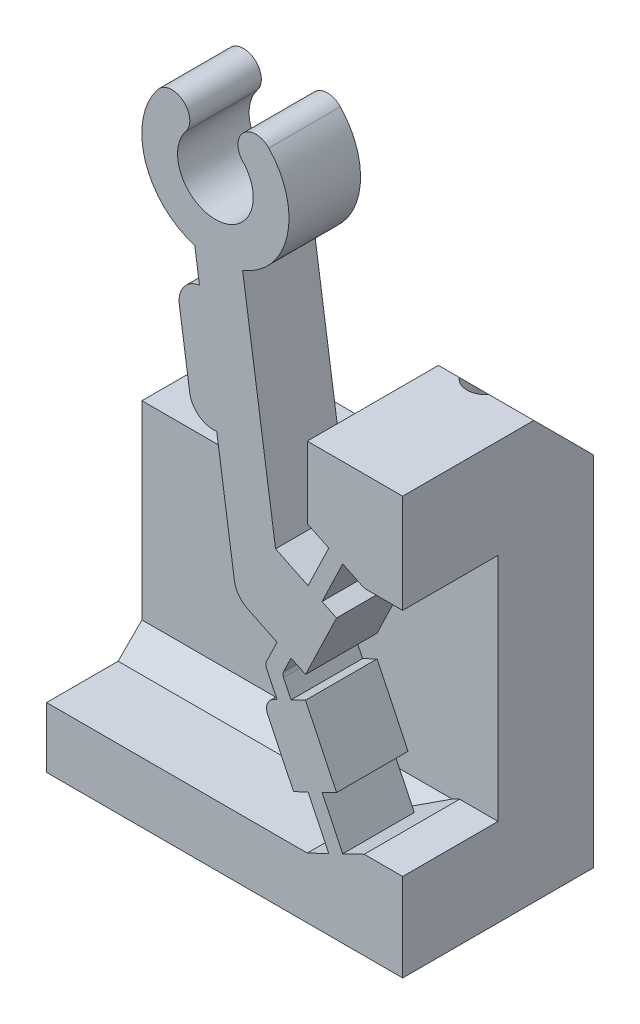
SolidWorks part; units mm, degrees
material "Nylon 6/12"
ref_plane "Front Plane" through (0, 0, 0) normal (0, 0, 1) x (1, 0, 0)
ref_plane "Top Plane" through (0, 0, 0) normal (0, 1, 0) x (1, 0, 0)
ref_plane "Right Plane" through (0, 0, 0) normal (1, 0, 0) x (0, 0, -1)
sketch "Sketch-SkeletonConfigUp" plane through (0, 0, 0) normal (0, 0, 1) x (1, 0, 0)
  line L0 (0, 0) -> (0, -50000) construction
  line L1 (2.4126, 7.5458) -> (2.4126, 0) construction
  line L2 (9.851, 11.9559) -> (4.5811, 12.0511) construction
  line L3 (4.5811, 12.0511) -> (2.4126, 7.5458) construction
  line L4 (2.4126, 7.5458) -> (4.5811, 3.0406) construction
  line L5 (4.5811, 12.0511) -> (6.3534, 17.2104) construction
  line L6 (2.4126, 7.5458) -> (-0.0324, 24.2377) construction
  line L7 (4.5811, 3.0406) -> (9.851, 11.9559) construction
  line L8 (-491.6261, -836.43) -> (9.851, 11.9559) construction
  line L9 (4.5811, 12.0511) -> (4.5811, 3.0406) construction
  line L10 (4.5811, 3.0406) -> (4.5811, -2.3626) construction
  line L11 (0, 0) -> (4.5811, 0) construction
  point P12 (0, 0)
  point P15 (2.4126, 7.9774)
  point P16 (4.5811, 2.192)
  point P17 (0, 0)
  dimension "D4" = 5.2707
  dimension "D5" = 119.553
  dimension "D7" = 5.4552
  dimension "D10" = 6.745
  dimension "D11" = 145.964
  dimension "D2" = 4.5811
  dimension "D3" = 2.1685
  dimension "D6" = 5
  dimension "D9" = 8.333
  dimension "D8" = 16.87
  dimension "D13" = 9.0105
  dimension "D12" = 3.0406
sketch "Sketch-SkeletonConfigDown" plane through (0, 0, 0) normal (0, 0, 1) x (1, 0, 0)
  line L0 (0, 0) -> (0, -50000) construction
  line L1 (4.5811, 12.0511) -> (4.5811, 3.0406) construction
  line L2 (9.851, 11.9559) -> (4.5811, 12.0511) construction
  line L3 (4.5811, 12.0511) -> (6.7497, 7.5458) construction
  line L4 (6.7497, 7.5458) -> (4.5811, 3.0406) construction
  line L5 (4.5811, 12.0511) -> (1.6542, 16.6546) construction
  line L6 (6.7497, 7.5458) -> (-7.8216, 16.0472) construction
  line L7 (4.5811, 3.0406) -> (9.851, 11.9559) construction
  line L8 (-477.4576, -812.4602) -> (9.851, 11.9559) construction
  line L10 (2.4126, 7.5458) -> (4.5811, 3.0406) construction
  line L11 (4.5811, 12.0511) -> (2.4126, 7.5458) construction
  line L12 (2.4126, 7.5458) -> (-0.0324, 24.2377) construction
  line L13 (4.5811, 12.0511) -> (6.3534, 17.2104) construction
  point P2 (4.7163, 6.3999)
  point P3 (4.5811, 1.9514)
  point P11 (5.1631, 6.5275)
  point P12 (4.5811, 9.9521)
  point P15 (4.5811, 13.1402)
  point P16 (6.2686, 7.5458)
  dimension "D4" = 5.2707
  dimension "D5" = 119.553
  dimension "D10" = 6.745
  dimension "D11" = 145.964
  dimension "D12" = 59.739
  dimension "D2" = 59.739
ref_plane "Plane-Cam Base" through (12.592, 0, 0) normal (1, 0, 0) x (0, 0, -1)
ref_plane "Plane-Down-to-Up Derailleur Clearance" through (10.092, 0, 0) normal (1, 0, 0) x (0, 0, -1)
ref_plane "Plane-Cam Cavity Roof" through (8.592, 0, 0) normal (1, 0, 0) x (0, 0, -1)
sketch "Sketch-SwitchBossUp" plane through (0, 0, 0) normal (0, 0, 1) x (1, 0, 0)
  line L8 (-0.8973, 21.2738) -> (-0.7004, 19.9295)
  line L9 (2.4126, 7.5458) -> (-0.0324, 24.2377) construction
  line L15 (2.5535, 6.5038) -> (3.1392, 6.7857) construction
  line L16 (2.4126, 7.5458) -> (4.5811, 3.0406) construction
  line L19 (3.8546, 11.291) -> (4.4403, 11.0091) construction
  line L22 (4.722, 13.0931) -> (5.3077, 12.8112) construction
  line L23 (2.5535, 8.5878) -> (1.9453, 8.8806)
  line L32 (4.874, 3.1815) -> (4.2883, 2.8996) construction
  line L40 (2.0519, 7.5458) -> (2.7733, 7.5458) construction
  line L66 (-0.0324, 27.8193) -> (-0.0324, 50027.8193) construction
  line L74 (-1.1101, 15.8268) -> (-1.5449, 18.7952)
  line L81 (6.2087, 2.7142) -> (10.695, 2.7142)
  line L82 (2.0299, 15.0897) -> (2.4901, 11.9478) construction
  line L88 (3.8209, 16.5268) -> (7.1146, 16.5268)
  line L92 (4.3979, 5.7269) -> (2.5958, 4.8595) construction
  line L95 (2.0299, 15.0897) -> (1.1101, 21.3694) construction
  line L96 (10.695, 2.7142) -> (10.695, 3.0949) construction
  line L97 (1.57, 18.2295) -> (0.9411, 17.592) construction
  line L101 (2.8463, 6.6448) -> (2.4126, 7.5458) construction
  line L103 (-0.0324, 24.2377) -> (1.6643, 25.8455) construction
  line L107 (2.5535, 8.5878) -> (3.1392, 8.3059) construction
  line L109 (-0.0324, 24.2377) -> (-1.8559, 25.7002) construction
  line L114 (3.7474, 7.0785) -> (3.1392, 6.7857)
  line L115 (7.1146, 16.5268) -> (13.4267, 16.5268)
  line L116 (13.4267, 16.5268) -> (13.4267, -0.9732)
  line L117 (13.4267, -0.9732) -> (5.2774, -0.9732)
  line L119 (10.695, 12.3775) -> (10.695, 2.7142)
  line L122 (4.722, 1.9985) -> (3.8209, 1.5648)
  line L123 (5.3077, 2.2805) -> (6.2087, 2.7142)
  line L125 (12.072, 7.7768) -> (13.4267, 7.7768) construction
  line L127 (3.1392, 8.3059) -> (3.7474, 8.0132)
  line L133 (4.2883, 12.1921) -> (4.874, 11.9101) construction
  line L134 (3.7474, 8.0132) -> (5.0485, 10.7163)
  line L135 (4.4403, 11.0091) -> (5.0485, 10.7163)
  line L142 (3.8209, 1.5648) -> (3.8209, -0.9732)
  line L143 (12.0045, 19.1883) -> (12.0045, 16.6962) construction
  line L145 (12.0045, 16.6883) -> (12.0045, -49992.0368) construction
  line L150 (3.8209, -0.9732) -> (5.2774, -0.9732)
  line L152 (4.722, 13.0931) -> (3.8546, 11.291)
  line L153 (5.3077, 12.8112) -> (4.4403, 11.0091)
  line L169 (3.8546, 3.8007) -> (4.722, 1.9985)
  line L170 (5.3077, 2.2805) -> (4.4403, 4.0826)
  line L177 (4.4403, 4.0826) -> (3.8546, 3.8007) construction
  line L191 (2.5535, 6.5038) -> (1.9453, 6.2111)
  line L207 (12.0045, 16.6962) -> (12.0045, 16.6883) construction
  line L209 (12.0045, 19.1883) -> (12.0045, 16.6883) construction
  line L217 (3.8546, 11.291) -> (2.4901, 11.9478)
  line L218 (4.4403, 4.0826) -> (5.0485, 4.3753)
  line L225 (2.4901, 11.9478) -> (1.1101, 21.3694)
  line L226 (3.8209, 13.5268) -> (3.8209, 16.5268)
  line L235 (-0.7004, 19.9295) -> (0.8401, 9.4125) construction
  line L236 (1.9453, 6.2111) -> (3.2464, 3.5079)
  line L237 (0.8401, 9.4125) -> (0.0243, 14.9823)
  line L241 (2.4126, 7.5458) -> (2.8463, 8.4469) construction
  line L243 (3.1392, 6.7857) -> (2.8255, 7.4374)
  line L244 (2.8255, 7.6543) -> (3.1392, 8.3059)
  line L245 (2.5535, 6.5038) -> (2.1041, 7.4374)
  line L246 (2.1041, 7.6543) -> (2.5535, 8.5878)
  line L247 (3.7474, 7.0785) -> (5.0485, 4.3753)
  line L248 (4.722, 1.9985) -> (5.3077, 2.2805) construction
  line L249 (3.8546, 3.8007) -> (3.2464, 3.5079)
  line L250 (1.9453, 8.8806) -> (3.2464, 11.5838) construction
  line L251 (4.5811, 12.0511) -> (2.4126, 7.5458) construction
  line L252 (2.5958, 10.2322) -> (4.3979, 9.3648) construction
  line L253 (3.2464, 11.5838) -> (2.4901, 11.9478) construction
  line L254 (1.9453, 8.8806) -> (0.8401, 9.4125)
  line L255 (4.722, 13.0931) -> (3.8209, 13.5268)
  line L256 (5.3077, 12.8112) -> (6.2087, 12.3775)
  line L257 (6.2087, 12.3775) -> (10.695, 12.3775)
  arc A0 (1.1101, 21.3694) -> (2.2088, 26.3614) centre (-0.0324, 24.2377) ccw
  arc A1 (-0.8973, 21.2738) -> (-2.4409, 26.1694) centre (-0.0324, 24.2377) cw
  arc A2 (-2.4409, 26.1694) -> (-1.2708, 25.2309) centre (-1.8559, 25.7002) cw
  arc A3 (2.2088, 26.3614) -> (1.1199, 25.3296) centre (1.6643, 25.8455) ccw
  arc A4 (-1.2708, 25.2309) -> (1.1199, 25.3296) centre (-0.0324, 24.2377) ccw
  arc A19 (-1.5449, 18.7952) -> (-0.7004, 19.9295) centre (-0.5554, 18.9401) cw
  circle A28 centre (-0.0324, 24.2377) radius 2.3375 construction
  arc A30 (-1.1101, 15.8268) -> (0.0243, 14.9823) centre (-0.1207, 15.9718) ccw
  arc A31 (2.8255, 7.4374) -> (2.8255, 7.6543) centre (3.0507, 7.5458) cw
  arc A32 (2.1041, 7.4374) -> (2.1041, 7.6543) centre (2.3294, 7.5458) cw
  point P3 (3.8091, 13.5268)
  point P5 (0, 0)
  point P6 (3.4969, 5.2932)
  point P7 (0, 0)
  point P16 (3.7601, 13.5561)
  point P28 (3.5462, 1.7741)
  point P33 (6.1777, 2.8466)
  point P37 (5.8406, 2.6366)
  point P45 (3.4969, 9.7985)
  point P50 (3.9347, 1.6196)
  point P52 (3.8382, 1.5732)
  point P54 (5.9324, 2.5678)
  point P66 (4.5811, 6.2164)
  point P165 (4.5811, 12.0511)
  dimension "D23" = 1.5875
  dimension "D24" = 0.75
  dimension "D21" = 0.25
  dimension "D9" = 17.5
  dimension "D8" = 0.65
  dimension "D27" = 0.65
  dimension "D26" = 2
  dimension "D3" = 1
  dimension "D5" = 1
  dimension "D16" = 2
  dimension "D28" = 2
  dimension "D18" = 3
  dimension "D29" = 2
  dimension "D30" = 1
  dimension "D31" = 5
  dimension "D4" = 0.8393
  dimension "D6" = 0.65
  dimension "D7" = 2
  dimension "D11" = 1
extrude "Boss-Switch Body" add sketch "Sketch-SwitchBossUp" along normal blind 3
sketch "Sketch1" plane through (0, 0, 0) normal (0, 0, -1) x (-1, 0, 0)
  line L0 (-7.8209, 2.7142) -> (-3.8209, 2.7142)
  line L1 (-7.8209, -0.9732) -> (-3.8209, -0.9732)
  line L2 (-7.8209, -0.9732) -> (-7.8209, 2.7142)
  line L4 (-3.8209, -0.9732) -> (-3.8209, 2.7142)
  line L5 (-3.8209, 12.3775) -> (-7.8209, 12.3775)
  line L10 (-7.8209, 12.3775) -> (-7.8209, 16.5268)
  line L12 (-7.8209, 16.5268) -> (-3.8209, 16.5268)
  line L14 (-3.8209, 16.5268) -> (-3.8209, 12.3775)
  line L20 (-6.2087, 2.7142) -> (-10.695, 2.7142) construction
  line L22 (-3.8209, -0.9732) -> (-13.4267, -0.9732) construction
  line L26 (-10.695, 12.3775) -> (-6.2087, 12.3775) construction
  line L32 (-3.8209, 1.5648) -> (-3.8209, -0.9732) construction
  point P1 (-7.8209, 2.6731)
  point P7 (-6.2087, 2.7142)
  point P8 (-3.8209, 1.5648)
  point P14 (-3.8209, 2.7142)
  point P18 (-3.7911, 1.5648)
  point P19 (-3.647, 2.4782)
  point P23 (-3.8209, 2.6758)
  dimension "D4" = 4
extrude "Boss-Flange Width" add sketch "Sketch1" along normal blind 5
ref_plane "Plane-Sta2Sit Groove" through (-0.0324, 0, 0) normal (1, 0, 0) x (0, 0, -1)
ref_plane "Plane-Cam Outer Surface" through (-12.1124, 0, 0) normal (1, 0, 0) x (0, 0, -1)
ref_plane "Plane-FlangeTop" through (-7.1124, 0, 0) normal (1, 0, 0) x (0, 0, -1)
sketch "Sketch2" plane through (-7.1124, 0, 0) normal (1, 0, 0) x (0, 0, -1)
  line L0 (5, 16.5268) -> (-3, 16.5268) construction
  line L1 (5, 12.3775) -> (1, 12.3775)
  line L2 (5, 12.3775) -> (5, 16.5268)
  line L3 (5, 16.5268) -> (1, 16.5268)
  line L4 (1, 12.3775) -> (1, 16.5268)
  line L5 (5, 12.3775) -> (0, 12.3775) construction
  line L10 (-3, -0.9732) -> (-3, 16.5268) construction
  line L11 (5, 1.5648) -> (-3, 1.5648)
  line L12 (5, 1.5648) -> (5, -0.9732)
  line L13 (5, -0.9732) -> (-3, -0.9732)
  line L14 (-3, 1.5648) -> (-3, -0.9732)
  line L15 (0, 7.5458) -> (0, 24.2377) construction
  line L17 (5, 2.7142) -> (5, -0.9732) construction
  line L19 (-3, 1.5648) -> (0, 1.5648) construction
  dimension "D1" = 1
extrude "Boss-Flange Height" add sketch "Sketch2" along normal up to surface (11.7404 mm away)
sketch "Sketch17" plane through (0, 1.5648, 0) normal (0, -1, 0) x (1, 0, 0)
  line L0 (7.8209, -5) -> (-7.1124, -5)
  line L1 (7.8209, -5) -> (-7.1124, -5) construction
  line L2 (-7.1124, -5) -> (-7.1124, -1)
  line L3 (-7.1124, -1) -> (7.8209, -1)
  line L4 (7.8209, -1) -> (7.8209, -5)
  line L5 (-7.1124, -1) -> (-7.1124, -5) construction
  line L6 (7.8209, -5) -> (7.8209, 0) construction
  line L7 (3.8209, -1) -> (-7.1124, -1) construction
extrude "Boss-Flange Support" add sketch "Sketch17" against normal up to surface (10.8127 mm away) up to face at (4.3619, 12.3775, -0.5)
sketch "Sketch27" plane through (0, 0, 0) normal (0, 0, 1) x (1, 0, 0)
  line L1 (3.8209, 13.5268) -> (6.2087, 12.3775)
  line L2 (6.2087, 12.3775) -> (3.8209, 12.3775)
  line L5 (3.8209, 12.3775) -> (3.8209, 13.5268)
  line L6 (3.8209, 12.3775) -> (7.8209, 12.3775) construction
  line L7 (6.2087, 12.3775) -> (5.0989, 12.3775) construction
  line L8 (6.2087, 2.7142) -> (3.8209, 2.7142)
  line L9 (3.8209, 2.7142) -> (3.8209, 1.5648)
  line L10 (3.8209, 1.5648) -> (6.2087, 2.7142)
extrude "Cut-Wall Gap" cut sketch "Sketch27" against normal up to surface (1 mm away) up to face at (2.0876, 8.2958, -1)
sketch "Sketch26" plane through (0, 0, -1) normal (0, 0, 1) x (1, 0, 0)
  line L0 (3.8209, 16.5268) -> (-7.1124, 16.5268)
  line L1 (-7.1124, 16.5268) -> (-7.1124, 10.5268)
  line L2 (-7.1124, 16.5268) -> (-7.1124, 1.5648) construction
  line L3 (-7.1124, 10.5268) -> (3.8209, 10.5268)
  line L4 (3.8209, 10.5268) -> (3.8209, 16.5268)
  dimension "D1" = 6
extrude "Cut-Cam Slope Clearance" cut sketch "Sketch26" against normal through all
ref_plane "Plane-Tap Depth" through (0, 5.5268, 0) normal (0, 1, 0) x (1, 0, 0)
sketch "Sketch-HolePositions" plane through (0, -0.9732, 0) normal (0, -1, 0) x (1, 0, 0)
  line L0 (-7.1124, -3) -> (7.8209, -3) construction
  line L1 (7.8209, -5) -> (-7.1124, -5) construction
  line L2 (7.8209, -5) -> (7.8209, 0) construction
  line L4 (-7.1124, -22.2167) -> (-7.1124, 22.2167) construction
  point P6 (-4.1124, -3)
  point P7 (5.3209, -3)
  dimension "D1" = 3
  dimension "D2" = 2.5
  dimension "D3" = 2
sketch "Sketch6" plane through (0, -0.9732, 0) normal (0, -1, 0) x (-1, 0, 0)
  point P0 (4.1124, 3)
  point P3 (-5.3209, 3)
hole_wizard "Tap Drill for M2x0.4 Tap1" positions "Sketch6" profile "Sketch5" hole size "M2x0.4" standard "ANSI Metric" end condition through all
sketch "Sketch5" plane through (-4.1124, -0.9732, -3) normal (1, 0, 0) x (0, 0, -1)
  line L0 (0, 0) -> (0, 27.5687)
  line L1 (0, 27.5687) -> (0.8, 27.5687)
  line L2 (0.8, 27.5687) -> (0.8, 0)
  line L5 (0.8, 0) -> (0, 0)
  line L11 (0, -6.35) -> (0, 107.95) construction
  dimension "Thru Hole Dia." = 1.6
  dimension "Thru Hole Depth" = 27.5687
sketch "Sketch9" plane through (0, -0.9732, 0) normal (0, -1, 0) x (1, 0, 0)
  point P0 (-4.1124, -3)
  point P3 (5.3209, -3)
hole_wizard "M2 Clearance Hole2" positions "Sketch9" profile "Sketch8" hole size "M2" standard "ANSI Metric"
sketch "Sketch8" plane through (-4.1124, -0.9732, -3) normal (1, 0, 0) x (0, 0, -1)
  line L0 (0, 0) -> (0, 7.221)
  line L1 (0, 7.221) -> (1.2, 6.5)
  line L2 (1.2, 6.5) -> (1.2, 0)
  line L5 (1.2, 0) -> (0, 0)
  line L10 (0, 7.221) -> (-1.2, 6.5) construction
  line L11 (0, -6.35) -> (0, 107.95) construction
  dimension "Hole Dia." = 2.4
  dimension "Hole Depth" = 6.5
  dimension "Drill Angle" = 118
sketch "Sketch-Measurements for Derailleur Ramps" [suppressed] plane through (0, 0, 0) normal (0, 0, 1) x (1, 0, 0)
  line L0 (2.8784, 16.9852) -> (4.2265, 19.8331)
  line L1 (3.5524, 18.4092) -> (3.0492, 18.6474)
  line L2 (1.9779, 11.0613) -> (4.4465, 28.5428) construction
  line L3 (3.0492, 18.6474) -> (-4.0642, 13.8428)
  line L4 (7.1843, 11.0614) -> (-9.9544, 15.2993) construction
  line L5 (3.0492, 18.6474) -> (2.1536, 12.3053)
  line L6 (2.1536, 12.3053) -> (-4.0642, 13.8428)
  line L7 (-0.5075, 16.2451) -> (-0.5075, 18.6474)
  line L8 (-0.5075, 18.6474) -> (3.0492, 18.6474)
  line L9 (7.1843, 11.0614) -> (1.9779, 11.0613)
  line L10 (5.8827, 8.6389) -> (3.2795, 8.6389)
  line L12 (7.1843, 11.0614) -> (4.5811, 6.2164) construction
  line L13 (4.5811, 8.6389) -> (4.5811, 8.7912)
  line L14 (4.5811, 6.2164) -> (5.8827, 8.6389)
  line L15 (1.9779, 11.0613) -> (4.5811, 6.2164) construction
  line L16 (3.2795, 8.6389) -> (4.5811, 6.2164)
  line L17 (5.8827, 8.6389) -> (5.8827, 8.7912)
  dimension "D1" = 3.5567
  dimension "D2" = 1.3016
sketch "Sketch12" [suppressed] plane through (0, 23.1883, 0) normal (0, 1, 0) x (1, 0, 0)
  line L0 (10.0045, 0) -> (12.0045, -3)
  line L1 (12.0045, -3) -> (12.0045, 0)
  line L2 (12.0045, 0) -> (10.0045, 0)
extrude "Cut-Up-to-Down Cantilever Slope" [suppressed] cut sketch "Sketch12" against normal up to next
ref_plane "Plane1" [suppressed] through (0, 6.9404, 0) normal (0, 1, 0) x (1, 0, 0)
sketch "Sketch-Derailleur Location" [suppressed] plane through (0, 6.9404, 0) normal (0, 1, 0) x (1, 0, 0)
  line L0 (12.9465, 0) -> (12.9465, -3)
  line L1 (4.2399, -3) -> (3.2603, -3) construction
  line L2 (-119237.4187, 0) -> (9.8143, 0) construction
  point P0 (12.9465, 0)
  point P8 (12.9465, -1.5)
ref_plane "Plane-Cantilever Cut" [suppressed] through (7.0848, 8.5204, -1.9058) normal (-0.6301, -0.7578, 0.1695) x (-0.7765, 0.6151, -0.1368)
sketch "Sketch14" [suppressed] plane through (7.0848, 8.5204, -1.9058) normal (-0.6301, -0.7578, 0.1695) x (-0.7765, 0.6151, -0.1368)
  line L0 (2.3023, -1.6911) -> (-0.3551, -1.6911)
  line L2 (2.3023, -4.3362) -> (2.3023, -1.6911)
  line L3 (-0.3551, -1.6911) -> (-0.3551, -4.4608)
  line L5 (-0.3551, -4.4608) -> (1.0087, -5.0843)
  line L6 (1.0087, -5.0843) -> (2.3023, -4.3362)
extrude "Cut-Down-to-Up Cantilever Slope" [suppressed] cut sketch "Sketch14" against normal up to next
ref_plane "Plane-Symmetry Plane" through (0, 0, 1.5) normal (0, 0, 1) x (1, 0, 0)
sketch "Sketch-Cable Center Point" plane through (0, 0, 1.5) normal (0, 0, 1) x (1, 0, 0)
  line L0 (-0.0324, 24.2377) -> (0.0827, 23.4523)
  line L1 (2.4126, 7.5458) -> (-0.0324, 24.2377) construction
  point P0 (-0.0324, 24.2377)
  dimension "D1" = 0.7937
chamfer "Chamfer-Flange Support" [suppressed] distance 1.5 angle 45
chamfer "Chamfer-Flange Support 3" distance 1 angle 45 1 edges at (-1.6457, 1.5648, -1)
sketch "Sketch25" plane through (0, 0, 3) normal (0, 0, 1) x (1, 0, 0)
  line L0 (13.4267, 16.5268) -> (13.4267, -0.9732)
  line L1 (13.4267, -0.9732) -> (7.8209, -0.9732)
  line L2 (-7.1124, -0.9732) -> (13.4267, -0.9732) construction
  line L3 (7.8209, -0.9732) -> (7.8209, 16.5268)
  line L4 (13.4267, 16.5268) -> (3.8209, 16.5268) construction
  line L5 (7.8209, 16.5268) -> (13.4267, 16.5268)
  line L6 (7.8209, 12.3775) -> (7.8209, 2.7142) construction
extrude "Cut-Base Removal" cut sketch "Sketch25" against normal up to surface (3 mm away) up to face at (2.3566, 11.6177, 0)
chamfer "Chamfer8" distance 2.5 angle 45 1 edges at (5.8209, 16.5268, -5)
sketch "Sketch28" plane through (0, -0.9732, 0) normal (0, -1, 0) x (1, 0, 0)
  line L0 (-7.1124, 3) -> (7.8209, 3)
  line L1 (7.8209, 3) -> (7.8209, 0)
  line L3 (7.8209, 0) -> (7.8209, -5)
  line L4 (7.8209, -5) -> (-7.1124, -5)
  line L5 (-7.1124, -5) -> (-7.1124, 3)
  circle A0 centre (5.3209, -3) radius 1.2 construction
  circle A1 centre (-4.1124, -3) radius 1.2 construction
  circle A2 centre (5.3209, -3) radius 1.2
  circle A3 centre (-4.1124, -3) radius 1.2
fillet "Fillet1" radius 1 1 edges at (0.8401, 9.4125, 1.5)
fillet "Fillet2" radius 0.5 1 edges at (1.9453, 6.2111, 1.5)
equation "\"axle-diameter\"=2"
equation "\"switch-thickness\"=12"
equation "\"base-width\"=4.0"
equation "\"axle-bushing-radius\"=3"
equation "\"clearance\"= 0.25"
equation "\"arm-width\"=1.5"
equation "\"min-diameter\"=70"
equation "\"alpha\"=143.6120"
equation "\"gamma\"=119.5526"
equation "\"delta\"=145.9637"
equation "\"epsilon\"=6.7452"
equation "\"l_AB\"=8.8212"
equation "\"l_AC\"=4.4914"
equation "\"l_BD\"=5.2707"
equation "\"l_CD\"=3.8848"
equation "\"l_CE\"=10.9181"
equation "\"l_DF\"=5.4552"
equation "\"l_OA\"=7.7221"
equation "\"D4@Sketch-SkeletonConfigUp\" = \"l_BD\""
equation "\"D5@Sketch-SkeletonConfigUp\" = \"gamma\""
equation "\"D7@Sketch-SkeletonConfigUp\" = \"l_DF\""
equation "\"D_groove\"=3.175"
equation "\"D5@Sketch-SkeletonConfigDown\" = \"gamma\""
equation "\"D4@Sketch-SkeletonConfigDown\" = \"l_BD\""
equation "\"hinge_length\"=1.5"
equation "\"hinge_depth\"=0.25"
equation "\"D10@Sketch-SkeletonConfigUp\"=\"epsilon\""
equation "\"D11@Sketch-SkeletonConfigUp\"=\"delta\""
equation "\"D11@Sketch-SkeletonConfigDown\"=\"delta\""
equation "\"D10@Sketch-SkeletonConfigDown\"=\"epsilon\""
equation "\"EE_dx\"=8.9056"
equation "\"EE_dy\"=8.1898"
equation "\"r_groove\"=\"D_groove\"/2"
equation "\"t_wall\"=25.4/16"
equation "\"width_lower\"=\"D_groove\"+\"t_wall\""
equation "\"cable_to_bottom\"=30.6257"
equation "\"switch_EE-up_base_dy\"=24"
equation "\"switch_EE-down_base_dy\"=16"
equation "\"D_axle\"=25.4/8"
equation "\"D_up_to_down\"=16"
equation "\"D_down_to_up\"=25"
equation "\"t_cam_base\"=7.5"
equation "\"D23@Sketch-SwitchBossUp\"=\"D_groove\"/2"
equation "\"D1@Sketch-Cable Center Point\"=\"D_groove\"/4"
